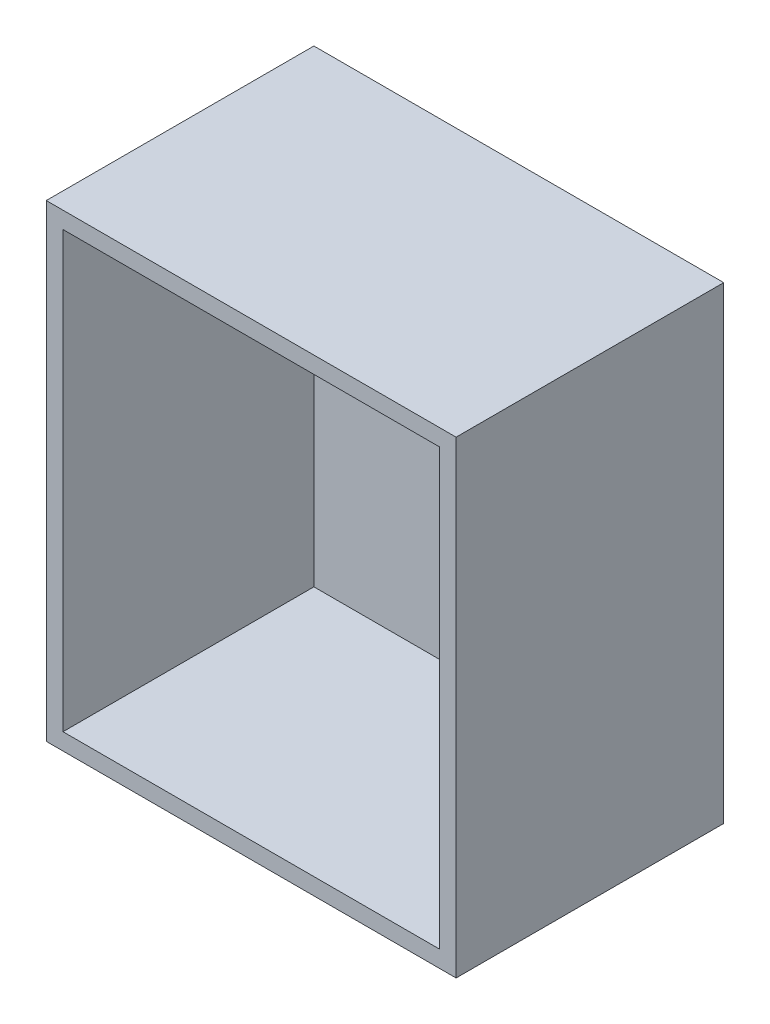
SolidWorks part; units mm, degrees
ref_plane "Piano frontale" through (0, 0, 0) normal (0, 0, 1) x (1, 0, 0)
ref_plane "Piano superiore" through (0, 0, 0) normal (0, 1, 0) x (1, 0, 0)
ref_plane "Piano destro" through (0, 0, 0) normal (1, 0, 0) x (0, 0, -1)
sketch "Schizzo1" plane through (0, 0, 0) normal (0, 0, 1) x (1, 0, 0)
  line L1 (0, 0) -> (49, 0)
  line L2 (0, 0) -> (0, 56)
  line L3 (0, 56) -> (49, 56)
  line L4 (49, 0) -> (49, 56)
  dimension "D1" = 49
  dimension "D2" = 56
extrude "Estrusione-Estrusione1" add sketch "Schizzo1" along normal blind 2
sketch "Schizzo3" plane through (0, 0, 2) normal (0, 0, 1) x (1, 0, 0)
  line L0 (49, 0) -> (49, 56) construction
  line L1 (0, 56) -> (49, 56)
  line L2 (0, 56) -> (0, 54)
  line L3 (0, 54) -> (49, 54)
  line L4 (49, 56) -> (49, 54)
  dimension "D1" = 2
extrude "Estrusione-Estrusione2" add sketch "Schizzo3" along normal blind 30
sketch "Schizzo4" plane through (0, 0, 2) normal (0, 0, 1) x (1, 0, 0)
  line L0 (0, 0) -> (49, 0) construction
  line L1 (49, 54) -> (47, 54)
  line L2 (49, 54) -> (49, 0)
  line L3 (49, 0) -> (47, 0)
  line L4 (47, 54) -> (47, 0)
  dimension "D1" = 2
extrude "Estrusione-Estrusione3" add sketch "Schizzo4" along normal blind 30
sketch "Schizzo5" plane through (0, 0, 2) normal (0, 0, 1) x (1, 0, 0)
  line L0 (0, 54) -> (0, 0) construction
  line L1 (47, 0) -> (0, 0)
  line L2 (47, 0) -> (47, 2)
  line L3 (47, 2) -> (0, 2)
  line L4 (0, 0) -> (0, 2)
  dimension "D1" = 2
extrude "Estrusione-Estrusione4" add sketch "Schizzo5" along normal blind 30
sketch "Schizzo6" plane through (0, 0, 2) normal (0, 0, 1) x (1, 0, 0)
  line L0 (47, 2) -> (0, 2) construction
  line L1 (0, 54) -> (2, 54)
  line L2 (0, 54) -> (0, 2)
  line L3 (0, 2) -> (2, 2)
  line L4 (2, 54) -> (2, 2)
  dimension "D1" = 2
extrude "Estrusione-Estrusione5" add sketch "Schizzo6" along normal blind 30
sketch "Schizzo7" plane through (0, 0, 2) normal (0, 0, 1) x (1, 0, 0)
  line L1 (2, 2) -> (2, 54) construction
  line L4 (2, 43.7) -> (27, 43.7)
  line L5 (2, 43.7) -> (2, 46.7)
  line L6 (2, 46.7) -> (27, 46.7)
  line L7 (27, 43.7) -> (27, 46.7)
  dimension "D2" = 3
  dimension "D3" = 25
extrude "Estrusione-Estrusione6" add sketch "Schizzo7" along normal blind 13.3
sketch "Schizzo9" plane through (0, 0, 2) normal (0, 0, 1) x (1, 0, 0)
  line L0 (2, 54) -> (47, 54) construction
  line L1 (47, 2) -> (43.5, 2)
  line L2 (47, 2) -> (47, 54)
  line L3 (47, 54) -> (43.5, 54)
  line L4 (43.5, 2) -> (43.5, 54)
  dimension "D1" = 3.5
extrude "Estrusione-Estrusione7" add sketch "Schizzo9" along normal blind 13.3
sketch "Schizzo10" plane through (0, 0, 15.3) normal (0, 0, 1) x (1, 0, 0)
  line L5 (4, 45.95) -> (8, 45.95)
  line L6 (4, 45.95) -> (4, 44.45)
  line L7 (4, 44.45) -> (8, 44.45)
  line L8 (8, 45.95) -> (8, 44.45)
  line L11 (26, 45.95) -> (22, 45.95)
  line L12 (26, 45.95) -> (26, 44.45)
  line L13 (26, 44.45) -> (22, 44.45)
  line L14 (22, 45.95) -> (22, 44.45)
  point P17 (26, 45.2)
  dimension "D3" = 1.5
  dimension "D4" = 4
  dimension "D6" = 4
extrude "Taglio-Estrusione1" cut sketch "Schizzo10" against normal blind 6
sketch "Schizzo11" plane through (0, 0, 15.3) normal (0, 0, 1) x (1, 0, 0)
  line L4 (46, 45.95) -> (44.5, 45.95)
  line L5 (46, 45.95) -> (46, 44.45)
  line L6 (46, 44.45) -> (44.5, 44.45)
  line L7 (44.5, 45.95) -> (44.5, 44.45)
  dimension "D2" = 1.5
  dimension "D3" = 1.5
extrude "Taglio-Estrusione2" cut sketch "Schizzo11" against normal blind 6
sketch "Schizzo12" plane through (0, 45.95, 0) normal (0, -1, 0) x (-1, 0, 0)
  line L0 (-8, -9.3) -> (-8, -15.3) construction
  line L1 (-4, -15.3) -> (-8, -15.3)
  line L2 (-4, -15.3) -> (-4, -14.3)
  line L3 (-4, -14.3) -> (-8, -14.3)
  line L4 (-8, -15.3) -> (-8, -14.3)
  dimension "D1" = 1
extrude "Taglio-Estrusione3" cut sketch "Schizzo12" against normal blind 0.75
sketch "Schizzo13" plane through (0, 44.45, 0) normal (0, 1, 0) x (1, 0, 0)
  line L0 (8, -9.3) -> (8, -15.3) construction
  line L1 (4, -15.3) -> (8, -15.3)
  line L2 (4, -15.3) -> (4, -14.3)
  line L3 (4, -14.3) -> (8, -14.3)
  line L4 (8, -15.3) -> (8, -14.3)
  dimension "D1" = 1
extrude "Taglio-Estrusione4" cut sketch "Schizzo13" against normal blind 0.75
sketch "Schizzo14" plane through (0, 45.95, 0) normal (0, -1, 0) x (-1, 0, 0)
  line L0 (-26, -9.3) -> (-26, -15.3) construction
  line L1 (-22, -15.3) -> (-26, -15.3)
  line L2 (-22, -15.3) -> (-22, -14.3)
  line L3 (-22, -14.3) -> (-26, -14.3)
  line L4 (-26, -15.3) -> (-26, -14.3)
  dimension "D1" = 1
extrude "Taglio-Estrusione5" cut sketch "Schizzo14" against normal blind 0.75
sketch "Schizzo15" plane through (0, 44.45, 0) normal (0, 1, 0) x (1, 0, 0)
  line L0 (26, -9.3) -> (26, -15.3) construction
  line L1 (22, -15.3) -> (26, -15.3)
  line L2 (22, -15.3) -> (22, -14.3)
  line L3 (22, -14.3) -> (26, -14.3)
  line L4 (26, -15.3) -> (26, -14.3)
  dimension "D1" = 1
extrude "Taglio-Estrusione6" cut sketch "Schizzo15" against normal blind 0.75
sketch "Schizzo21" plane through (0, 0, 15.3) normal (0, 0, 1) x (1, 0, 0)
  line L0 (43.5, 54) -> (43.5, 2) construction
  line L1 (44.5, 45.95) -> (43.5, 45.95)
  line L2 (44.5, 45.95) -> (44.5, 44.45)
  line L3 (44.5, 44.45) -> (43.5, 44.45)
  line L4 (43.5, 45.95) -> (43.5, 44.45)
extrude "Taglio-Estrusione7" cut sketch "Schizzo21" against normal blind 1
sketch "Schizzo23" plane through (0, 0, 15.3) normal (0, 0, 1) x (1, 0, 0)
  line L1 (43.5, 45.95) -> (46, 45.95)
  line L2 (43.5, 45.95) -> (43.5, 46.7)
  line L3 (43.5, 46.7) -> (46, 46.7)
  line L4 (46, 45.95) -> (46, 46.7)
  dimension "D1" = 0.75
extrude "Taglio-Estrusione8" cut sketch "Schizzo23" against normal blind 1
sketch "Schizzo24" plane through (0, 0, 15.3) normal (0, 0, 1) x (1, 0, 0)
  line L1 (43.5, 44.45) -> (45.9968, 44.45)
  line L2 (43.5, 44.45) -> (43.5, 43.7)
  line L3 (43.5, 43.7) -> (45.9968, 43.7)
  line L4 (45.9968, 44.45) -> (45.9968, 43.7)
  dimension "D1" = 0.75
extrude "Taglio-Estrusione9" cut sketch "Schizzo24" against normal blind 1
sketch "Schizzo26" plane through (0, 0, 15.3) normal (0, 0, 1) x (1, 0, 0)
  line L0 (47, 54) -> (47, 2) construction
  line L1 (45.9968, 43.7) -> (47, 43.7)
  line L2 (45.9968, 43.7) -> (45.9968, 46.7)
  line L3 (45.9968, 46.7) -> (47, 46.7)
  line L4 (47, 43.7) -> (47, 46.7)
  dimension "D1" = 3
extrude "Taglio-Estrusione10" cut sketch "Schizzo26" against normal blind 1
sketch "Schizzo27" plane through (0, 0, 15.3) normal (0, 0, 1) x (1, 0, 0)
  line L1 (26, 46.7) -> (27, 46.7)
  line L2 (26, 46.7) -> (26, 43.7)
  line L3 (26, 43.7) -> (27, 43.7)
  line L4 (27, 46.7) -> (27, 43.7)
extrude "Taglio-Estrusione11" cut sketch "Schizzo27" against normal blind 1
sketch "Schizzo28" plane through (0, 0, 15.3) normal (0, 0, 1) x (1, 0, 0)
  line L1 (47, 2) -> (47, 43.7) construction
  line L2 (43.5, 43.7) -> (43.5, 2) construction
  line L3 (47, 13.3) -> (43.5, 13.3)
  line L4 (47, 13.3) -> (47, 17.3)
  line L5 (47, 17.3) -> (43.5, 17.3)
  line L6 (43.5, 13.3) -> (43.5, 17.3)
  line L7 (47, 17.3) -> (26, 17.3) construction
extrude "Taglio-Estrusione12" cut sketch "Schizzo28" against normal blind 1
sketch "Schizzo33" plane through (0, 0, 15.3) normal (0, 0, 1) x (1, 0, 0)
  line L1 (43.5, 43.7) -> (43.5, 17.3) construction
  line L3 (43.5, 28.5) -> (47, 28.5)
  line L4 (43.5, 28.5) -> (43.5, 32.5)
  line L5 (43.5, 32.5) -> (47, 32.5)
  line L6 (47, 28.5) -> (47, 32.5)
extrude "Taglio-Estrusione16" cut sketch "Schizzo33" against normal blind 1
